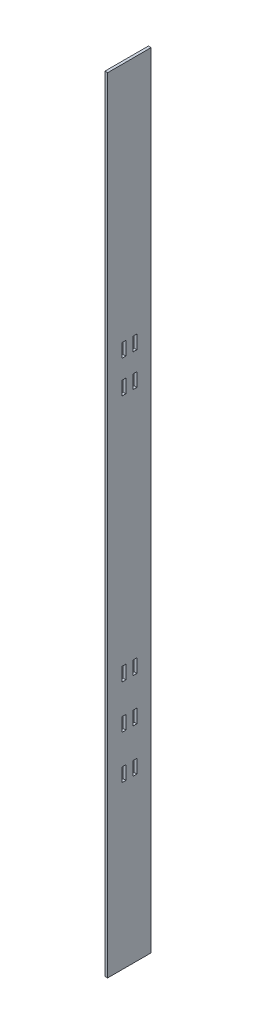
SolidWorks part; units mm, degrees
ref_plane "Front Plane" through (0, 0, 0) normal (0, 0, 1) x (1, 0, 0)
ref_plane "Top Plane" through (0, 0, 0) normal (0, 1, 0) x (1, 0, 0)
ref_plane "Right Plane" through (0, 0, 0) normal (1, 0, 0) x (0, 0, -1)
sketch "Sketch1" plane through (0, 0, 0) normal (1, 0, 0) x (0, 0, -1)
  line L1 (-25.4, 457.2) -> (25.4, 457.2)
  line L2 (-25.4, 457.2) -> (-25.4, -457.2)
  line L3 (-25.4, -457.2) -> (25.4, -457.2)
  line L4 (25.4, 457.2) -> (25.4, -457.2)
  line L5 (-25.4, 457.2) -> (25.4, -457.2) construction
  line L6 (-25.4, -457.2) -> (25.4, 457.2) construction
  point P0 (0, 0)
  dimension "D1" = 914.4
  dimension "D2" = 50.8
extrude "Boss-Extrude1" add sketch "Sketch1" along normal blind 3.175
sketch "Sketch2" plane through (3.175, 0, 0) normal (1, 0, 0) x (0, 0, -1)
  line L0 (-25.4, -457.2) -> (25.4, -457.2) construction
  line L1 (4, -201.6125) -> (8.7625, -201.6125)
  line L2 (4, -201.6125) -> (4, -217.4875)
  line L3 (4, -217.4875) -> (8.7625, -217.4875)
  line L4 (8.7625, -201.6125) -> (8.7625, -217.4875)
  line L5 (4, -201.6125) -> (8.7625, -217.4875) construction
  line L6 (4, -217.4875) -> (8.7625, -201.6125) construction
  point P0 (6.3813, -209.55)
  dimension "D1" = 4.7625
  dimension "D2" = 15.875
  dimension "D3" = 239.7125
  dimension "D4" = 4
extrude "Cut-Extrude1" cut sketch "Sketch2" against normal through all
mirror "Mirror1" about plane through (0, 0, 0) normal (0, 0, 1) of "Cut-Extrude1"
pattern_linear "LPattern1" count 2 spacing 50.8 along (0, 1, 0) count 2 spacing 50.8 along (0, -1, 0) of "Mirror1"
sketch "Sketch3" plane through (3.175, 0, 0) normal (1, 0, 0) x (0, 0, -1)
  line L0 (8.7625, -166.6875) -> (8.7625, -150.8125) construction
  line L1 (4, 138.1125) -> (8.7625, 138.1125)
  line L2 (4, 138.1125) -> (4, 122.2375)
  line L3 (4, 122.2375) -> (8.7625, 122.2375)
  line L4 (8.7625, 138.1125) -> (8.7625, 122.2375)
  line L5 (4, 138.1125) -> (8.7625, 122.2375) construction
  line L6 (4, 122.2375) -> (8.7625, 138.1125) construction
  line L7 (8.7625, -150.8125) -> (4, -150.8125) construction
  line L8 (4, -150.8125) -> (4, -166.6875) construction
  line L9 (0, 0) -> (0, 52.1648) construction
  line L10 (-4, 122.2375) -> (-8.7625, 138.1125) construction
  line L11 (-4, 138.1125) -> (-8.7625, 122.2375) construction
  line L12 (-8.7625, 138.1125) -> (-8.7625, 122.2375)
  line L13 (-4, 122.2375) -> (-8.7625, 122.2375)
  line L14 (-4, 138.1125) -> (-4, 122.2375)
  line L15 (-4, 138.1125) -> (-8.7625, 138.1125)
  point P0 (6.3812, 130.175)
  point P18 (-6.3812, 130.175)
  dimension "D1" = 273.05
extrude "Cut-Extrude2" cut sketch "Sketch3" against normal through all
pattern_linear "LPattern2" count 2 spacing 38.1 along (0, 1, 0) of "Cut-Extrude2"
